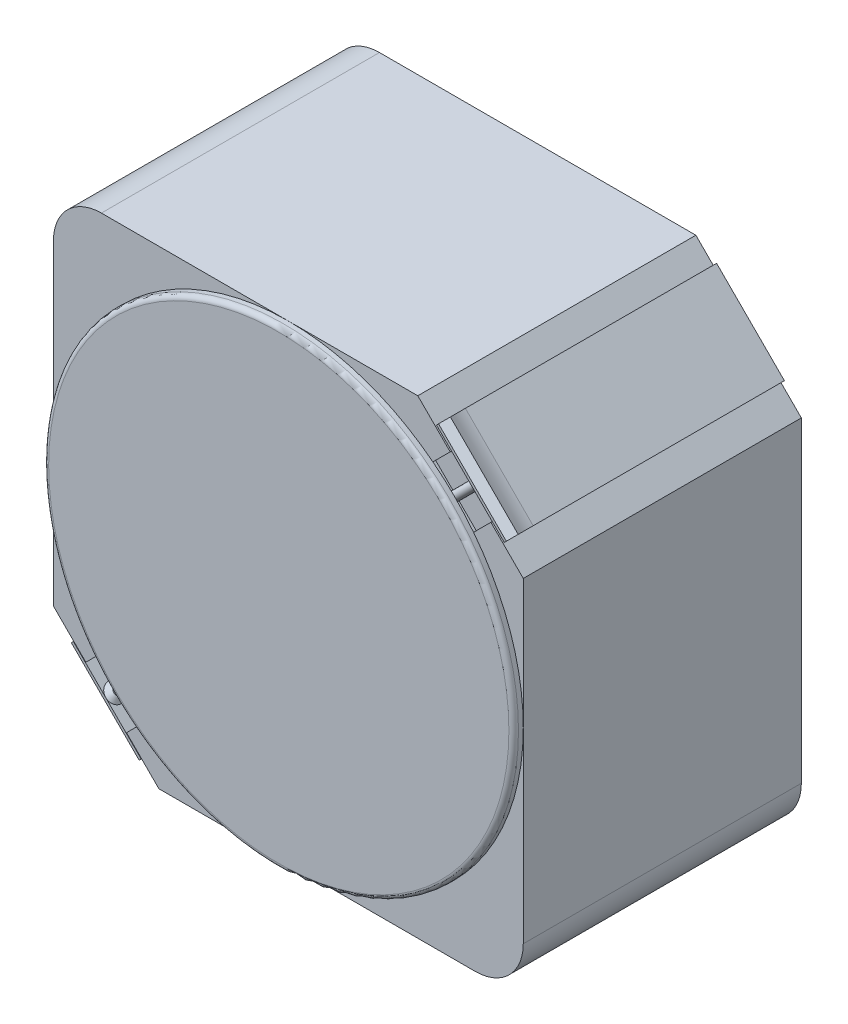
SolidWorks part; units mm, degrees
ref_plane "Спереди" through (0, 0, 0) normal (0, 0, 1) x (1, 0, 0)
ref_plane "Сверху" through (0, 0, 0) normal (0, 1, 0) x (1, 0, 0)
ref_plane "Справа" through (0, 0, 0) normal (1, 0, 0) x (0, 0, -1)
sketch "Эскиз1" plane through (0, 0, 0) normal (0, 0, 1) x (1, 0, 0)
  line L0 (-2.45, -1.35) -> (-1.35, -2.45)
  line L1 (-1.95, 2.45) -> (1.35, 2.45)
  line L2 (-2.45, 1.95) -> (-2.45, -1.35)
  line L3 (-1.35, -2.45) -> (1.95, -2.45)
  line L4 (2.45, 1.35) -> (2.45, -1.95)
  line L5 (-2.45, 2.45) -> (2.45, -2.45) construction
  line L6 (-2.45, -2.45) -> (2.45, 2.45) construction
  line L7 (1.35, 2.45) -> (2.45, 1.35)
  arc A0 (-1.95, 2.45) -> (-2.45, 1.95) centre (-1.95, 1.95) ccw
  arc A1 (1.95, -2.45) -> (2.45, -1.95) centre (1.95, -1.95) ccw
  point P0 (0, 0)
  dimension "D1" = 0.5
  dimension "D2" = 4.9
extrude "Корпус" add sketch "Эскиз1" along normal blind 2.9 from offset 0.005
sketch "Эскиз2" plane through (0, 0, 2.905) normal (0, 0, 1) x (1, 0, 0)
  line L0 (-2.45, 1.95) -> (-2.45, -1.35) construction
  circle A0 centre (0, 0) radius 2.45
extrude "Сердечник" add sketch "Эскиз2" along normal blind 0.1 and the other way blind 1
fillet "Скругление1" radius 0.05 1 edges at (2.45, 0, 3.005)
ref_plane "Плоскость1" through (0.55, -0.55, 0) normal (0.7071, -0.7071, 0) x (0, 0, 1)
sketch "Эскиз6" plane through (0.55, -0.55, 0) normal (0.7071, -0.7071, 0) x (0, 0, 1)
  line L0 (2.813, -2.782) -> (2.9, -2.73)
  line L1 (2.9, -2.7) -> (0.03, -2.7)
  line L2 (2.62, -2.73) -> (0, -2.73)
  line L3 (0, -2.73) -> (0, -2.2)
  line L4 (0.03, -2.7) -> (0.03, -2.2)
  line L5 (0.03, -2.2) -> (0, -2.2)
  line L6 (2.9, -2.73) -> (2.9, -2.7)
  line L8 (0.005, -2.687) -> (2.905, -2.687) construction
  line L9 (2.905, -2.45) -> (2.905, -1.7324) construction
  line L11 (0.005, 0.3536) -> (0.005, 2.687) construction
  line L12 (2.905, -2.687) -> (0.005, -2.687) construction
  spline S0 degree 2 poles (2.62, -2.73) (2.7238, -2.7338) (2.813, -2.782) knots 0 0 0 1 1 1
  dimension "D2" = 0.5
  dimension "D3" = 0.013
  dimension "D4" = 0.025
  dimension "D5" = 0.005
  dimension "D6" = 0.082
  dimension "D7" = 0.087
  dimension "D8" = 120.867
  dimension "D9" = 0.28
  dimension "D10" = 0.1354
  dimension "D11" = 0.0295
  dimension "D12" = 0.03
extrude "вывод, бок" add sketch "Эскиз6" against normal blind 1 from offset 0.3 offset against normal yes
ref_point "Точка1"
ref_axis "Ось1" through (0, 0, 3.005) along (0, 0, -1)
sketch "Эскиз8" plane through (0, 0, 2.905) normal (0, 0, 1) x (1, 0, 0)
  line L0 (2.1121, 1.6879) -> (1.6879, 2.1121)
  line L2 (1.6879, 2.1121) -> (1.3357, 1.76)
  line L3 (-1.6879, -2.1121) -> (-1.3357, -1.76)
  line L4 (1.5479, 1.5479) -> (0, 0) construction
  line L5 (2.1121, 1.6879) -> (1.76, 1.3357)
  line L6 (1.76, 1.3357) -> (1.3357, 1.76)
  line L7 (-1.76, -1.3357) -> (-1.3357, -1.76)
  line L8 (-2.1121, -1.6879) -> (-1.76, -1.3357)
  line L9 (-2.1121, -1.6879) -> (-1.6879, -2.1121)
  line L10 (2.45, 1.35) -> (1.35, 2.45) construction
  dimension "D2" = 0.498
  dimension "D4" = 0.6
  dimension "D1" = 2
extrude "Вытянуть8" cut sketch "Эскиз8" against normal blind 0.2
sketch "Эскиз9" plane through (1.9092, 1.9092, 0) normal (-0.7071, -0.7071, 0) x (0, 0, 1)
  line L1 (0, 0) -> (2.804, 0) construction
  line L2 (2.9, 0.5222) -> (2.9, -0.4778) construction
  circle A0 centre (2.804, 0) radius 0.046
  dimension "D1" = 0.092
  dimension "D2" = 0.096
extrude "Бобышка-Вытянуть1" add sketch "Эскиз9" along normal up to next (0.511 mm away) and the other way blind 0.05 draft 45 from offset 0.05 other way draft outward yes
pattern_circular "Круговой массив3" count 2 over 360 about axis through (0, 0, 3.005) along (0, 0, -1) of "вывод, бок", "Бобышка-Вытянуть1"
sketch "Эскиз13" plane through (0, 0, 0.005) normal (0, 0, -1) x (-1, 0, 0)
  line L1 (-2.45, -1.95) -> (-2.45, 1.35) construction
  line L2 (0, -2.4) -> (0, 0) construction
  line L3 (2.45, 1.95) -> (2.45, -1.35) construction
  line L4 (1.5308, -2.2692) -> (1.35, -2.45) construction
  line L5 (1.6527, 0) -> (-1.6527, 0) construction
  line L6 (1.8, 0.7488) -> (2.4, 0.7488)
  line L7 (1.35, -2.45) -> (-1.95, -2.45) construction
  line L8 (2.4, 0.7488) -> (2.4, 1.3288)
  line L9 (1.3288, 2.4) -> (2.4, 1.3288)
  line L10 (-1.3288, 2.4) -> (1.3288, 2.4)
  line L11 (-2.4, 1.3288) -> (-1.3288, 2.4)
  line L12 (-2.4, -0.7488) -> (-1.8, -0.7488)
  line L13 (-2.4, -1.3288) -> (-2.4, -0.7488)
  line L16 (-2.4, -1.3288) -> (-1.3288, -2.4)
  line L17 (-2.4, 1.3288) -> (-2.4, 0.7488)
  line L18 (-1.3288, -2.4) -> (1.3288, -2.4)
  line L19 (1.3288, -2.4) -> (2.4, -1.3288)
  line L20 (2.4, -0.7488) -> (2.4, -1.3288)
  line L21 (1.8, -0.7488) -> (2.4, -0.7488)
  line L22 (-2.4, 0.7488) -> (-1.8, 0.7488)
  arc A0 (-1.8, -0.7488) -> (1.8, -0.7488) centre (0, 0) ccw
  arc A1 (-1.8, 0.7488) -> (1.8, 0.7488) centre (0, 0) cw
  circle A2 centre (0, 0) radius 2.45 construction
  dimension "D2" = 0.5004
  dimension "D3" = 0.6
  dimension "D5" = 0.05
  dimension "D6" = 0.0503
  dimension "D7" = 0.05
  dimension "D1" = 0.58
extrude "Выводы низ" add sketch "Эскиз13" along normal up to surface (0.005 mm away) up to face at (-1.7273, -1.7587, 0)
